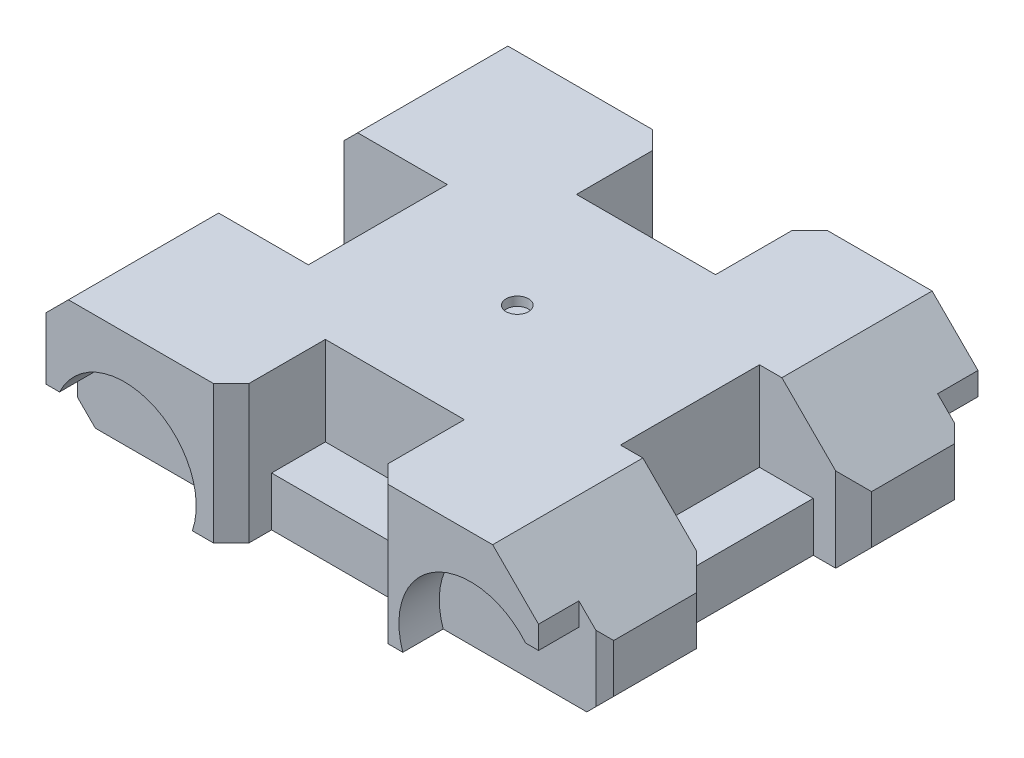
SolidWorks part; units mm, degrees
ref_plane "前视基准面" through (0, 0, 0) normal (0, 0, 1) x (1, 0, 0)
ref_plane "上视基准面" through (0, 0, 0) normal (0, 1, 0) x (1, 0, 0)
ref_plane "右视基准面" through (0, 0, 0) normal (1, 0, 0) x (0, 0, -1)
sketch "草图1" plane through (0, 0, 0) normal (0, 1, 0) x (1, 0, 0)
  line L1 (-294, 245) -> (294, 245)
  line L2 (-294, 245) -> (-294, -245)
  line L3 (-294, -245) -> (294, -245)
  line L4 (294, 245) -> (294, -245)
  line L5 (-294, 245) -> (294, -245) construction
  line L6 (-294, -245) -> (294, 245) construction
  point P0 (0, 0)
  dimension "D1" = 588
  dimension "D2" = 490
extrude "凸台-拉伸1" add sketch "草图1" along normal blind 154
sketch "草图2" plane through (0, 0, 245) normal (0, 0, 1) x (1, 0, 0)
  line L0 (294, 154) -> (294, 0) construction
  line L1 (-294, 0) -> (294, 0) construction
  circle A0 centre (-196.5, 26) radius 80
  circle A1 centre (189.5, 26) radius 80
  dimension "D2" = 160
  dimension "D1" = 386
  dimension "D3" = 104.5
  dimension "D4" = 26
extrude "切除-拉伸1" cut sketch "草图2" against normal blind 45
mirror "镜向1" about plane through (0, 0, 0) normal (0, 0, 1) of "切除-拉伸1"
sketch "草图3" plane through (0, 154, 0) normal (0, 1, 0) x (1, 0, 0)
  line L0 (0, 245) -> (0, 0) construction
  line L1 (294, 245) -> (-294, 245) construction
  line L2 (0, 0) -> (294, 0) construction
  line L4 (294, -245) -> (294, 245) construction
  line L5 (77.5, -140) -> (77.5, -245)
  line L6 (189, 77.5) -> (294, 77.5)
  line L7 (189, 77.5) -> (189, -77.5)
  line L8 (189, -77.5) -> (294, -77.5)
  line L9 (294, 77.5) -> (294, -77.5)
  line L10 (189, 77.5) -> (294, -77.5) construction
  line L11 (189, -77.5) -> (294, 77.5) construction
  line L12 (-77.5, 140) -> (77.5, 140)
  line L13 (-77.5, 140) -> (-77.5, 245)
  line L14 (-77.5, 245) -> (77.5, 245)
  line L15 (77.5, 140) -> (77.5, 245)
  line L16 (-77.5, 140) -> (77.5, 245) construction
  line L17 (-77.5, 245) -> (77.5, 140) construction
  line L18 (-77.5, -245) -> (77.5, -245)
  line L19 (-77.5, -140) -> (-77.5, -245)
  line L20 (-77.5, -140) -> (77.5, -140)
  line L21 (0, 0) -> (-294, 0) construction
  line L22 (-294, 245) -> (-294, -245) construction
  line L24 (-159, 77.5) -> (-294, 77.5)
  line L25 (-159, 77.5) -> (-159, -77.5)
  line L26 (-159, -77.5) -> (-294, -77.5)
  line L27 (-294, 77.5) -> (-294, -77.5)
  line L28 (-159, 77.5) -> (-294, -77.5) construction
  line L29 (-159, -77.5) -> (-294, 77.5) construction
  point P8 (241.5, 0)
  point P13 (0, 192.5)
  point P18 (0, -192.5)
  point P23 (-226.5, 0)
  dimension "D1" = 155
  dimension "D2" = 105
  dimension "D3" = 135
extrude "切除-拉伸2" cut sketch "草图3" against normal blind 99
chamfer "倒角1" distance 80 angle 45 2 edges at (294, 154, -161.25) (294, 154, 161.25)
sketch "草图4" plane through (0, 55, 0) normal (0, 1, 0) x (1, 0, 0)
  line L0 (294, 77.5) -> (189, 77.5) construction
  line L1 (294, -77.5) -> (249, -77.5)
  line L2 (294, -77.5) -> (294, 77.5)
  line L3 (294, 77.5) -> (249, 77.5)
  line L4 (249, -77.5) -> (249, 77.5)
  line L5 (77.5, 140) -> (77.5, 245) construction
  line L6 (-77.5, 245) -> (77.5, 245)
  line L7 (-77.5, 245) -> (-77.5, 200)
  line L8 (-77.5, 200) -> (77.5, 200)
  line L9 (77.5, 245) -> (77.5, 200)
  line L10 (77.5, -245) -> (77.5, -140) construction
  line L11 (-77.5, -245) -> (77.5, -245)
  line L12 (-77.5, -245) -> (-77.5, -200)
  line L13 (-77.5, -200) -> (77.5, -200)
  line L14 (77.5, -245) -> (77.5, -200)
  line L15 (-294, -77.5) -> (-159, -77.5) construction
  line L16 (-294, 77.5) -> (-244, 77.5)
  line L17 (-294, 77.5) -> (-294, -77.5)
  line L18 (-294, -77.5) -> (-244, -77.5)
  line L19 (-244, 77.5) -> (-244, -77.5)
  dimension "D1" = 45
  dimension "D2" = 50
extrude "切除-拉伸3" cut sketch "草图4" against normal through all
chamfer "倒角2" distance 20 angle 45 8 edges at (77.5, 77, -245) (-77.5, 77, -245) (-77.5, 77, 245) (77.5, 77, 245) (294, 37, 77.5) (294, 37, -77.5) (-294, 77, 77.5) (-294, 77, -77.5)
chamfer "倒角3" distance 35 angle 45 2 edges at (-294, 154, 171.25) (-294, 154, -171.25)
sketch "草图5" plane through (0, 55, 0) normal (0, 1, 0) x (1, 0, 0)
  line L4 (-159, 77.5) -> (-244, 77.5)
  line L5 (-244, 77.5) -> (-244, -77.5)
  line L6 (-244, -77.5) -> (-159, -77.5)
  line L7 (-159, -77.5) -> (-159, 77.5)
  line L8 (-159, 77.5) -> (-244, 77.5)
  line L9 (-244, 77.5) -> (-244, -77.5)
  line L10 (-244, -77.5) -> (-159, -77.5)
  line L11 (-159, -77.5) -> (-159, 77.5)
  dimension "D1" = 0
extrude "切除-拉伸4" cut sketch "草图5" against normal blind 47
sketch "草图6" plane through (0, 154, 0) normal (0, 1, 0) x (1, 0, 0)
  line L0 (-196.5, 200) -> (189.5, -200) construction
  line L1 (-116.5, 200) -> (-276.5, 200) construction
  line L2 (109.5, -200) -> (269.5, -200) construction
  circle A0 centre (-3.5, 0) radius 12.5
  dimension "D1" = 25
extrude "切除-拉伸5" cut sketch "草图6" against normal blind 10
chamfer "倒角4" distance 10 angle 45 2 edges at (-294, 59.5, -245) (-294, 59.5, 245)
sketch "草图7" plane through (0, 0, 0) normal (0, -1, 0) x (1, 0, 0)
  line L2 (265.1571, 200) -> (294, 200)
  line L3 (265.1571, 200) -> (265.1571, 245)
  line L4 (0, 0) -> (249, 0) construction
  line L5 (249, -77.5) -> (249, 77.5) construction
  line L7 (265.1571, 245) -> (294, 245)
  line L8 (294, 200) -> (294, 245)
  line L9 (265.1571, -200) -> (294, -200)
  line L10 (265.1571, -200) -> (265.1571, -245)
  line L11 (265.1571, -245) -> (294, -245)
  line L12 (294, -200) -> (294, -245)
extrude "切除-拉伸6" cut sketch "草图7" against normal through all
chamfer "倒角6" distance 10 angle 45 2 edges at (294, 37, -200) (294, 37, 200)
sketch "草图8" plane through (0, 0, 245) normal (0, 0, 1) x (1, 0, 0)
  line L0 (265.1571, 77.4214) -> (250.7849, 77.4214)
  line L1 (265.1571, 102.8429) -> (265.1571, 52) construction
  line L2 (265.1571, 52) -> (265.1571, 77.4214)
  arc A0 (265.1571, 52) -> (113.8429, 0) centre (189.5, 26) ccw construction
  arc A1 (265.1571, 52) -> (250.7849, 77.4214) centre (189.5, 26) ccw
extrude "切除-拉伸7" cut sketch "草图8" against normal up to surface (45 mm away) up to face at (237.2314, 62.9, 200)
extrude "切除-拉伸8" cut sketch "草图8<2>" along normal up to surface (-445 mm away) from surface up to face at (237.2314, 62.9, -200) starting at face at (171.1929, 89.75, -245)
sketch "草图8<2>" plane through (0, 0, 245) normal (0, 0, 1) x (1, 0, 0) same geometry as "草图8"
sketch "草图9" plane through (-294, 0, 0) normal (-1, 0, 0) x (0, 0, 1)
  line L0 (245, 129) -> (245, 0) construction
  line L1 (200, 0) -> (245, 0)
  line L2 (200, 0) -> (200, 60)
  line L3 (200, 60) -> (245, 60)
  line L4 (245, 0) -> (245, 60)
  line L5 (0, 0) -> (0, 154) construction
  line L6 (77.5, 154) -> (-77.5, 154) construction
  line L7 (-245, 0) -> (-245, 60)
  line L8 (-200, 60) -> (-245, 60)
  line L9 (-200, 0) -> (-200, 60)
  line L10 (-200, 0) -> (-245, 0)
  dimension "D1" = 60
extrude "切除-拉伸9" cut sketch "草图9" against normal blind 50
chamfer "倒角7" distance 20 angle 45 4 edges at (-294, 0, -148.75) (-294, 0, 148.75) (294, 0, -143.75) (294, 0, 143.75)
